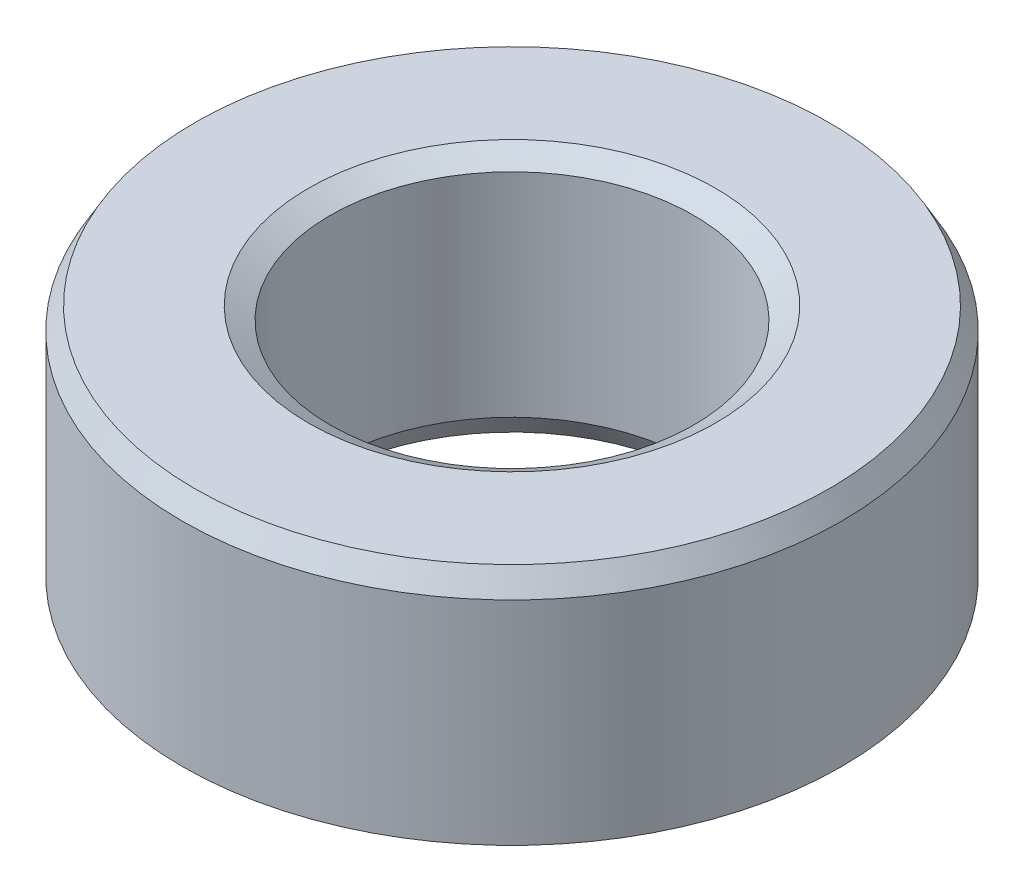
SolidWorks part; units mm, degrees
ref_plane "Front Plane" through (0, 0, 0) normal (0, 0, 1) x (1, 0, 0)
ref_plane "Top Plane" through (0, 0, 0) normal (0, 1, 0) x (1, 0, 0)
ref_plane "Right Plane" through (0, 0, 0) normal (1, 0, 0) x (0, 0, -1)
sketch "Sketch1" plane through (0, 0, 0) normal (0, 1, 0) x (1, 0, 0)
  circle A0 centre (0, 0) radius 60
  dimension "SLEEVE_OD" = 120
extrude "Boss-Extrude1" add sketch "Sketch1" along normal blind 44.9283
sketch "Sketch2" plane through (0, 0, 0) normal (0, 1, 0) x (1, 0, 0)
  circle A0 centre (0, 0) radius 33.0722
  dimension "BORE_D" = 66.1444
extrude "Cut-Extrude1" cut sketch "Sketch2" along normal through all
chamfer "Chamfer1" distance 3.9624 angle 30 4 edges at (0, 44.9283, 33.0722) (0, 0, 33.0722) (0, 0, 60) (0, 44.9283, 60) first distance on face at (0, 44.9283, 33.0722) first distance on face at (0, 0, 33.0722) first distance on face at (0, 44.9283, 60)
